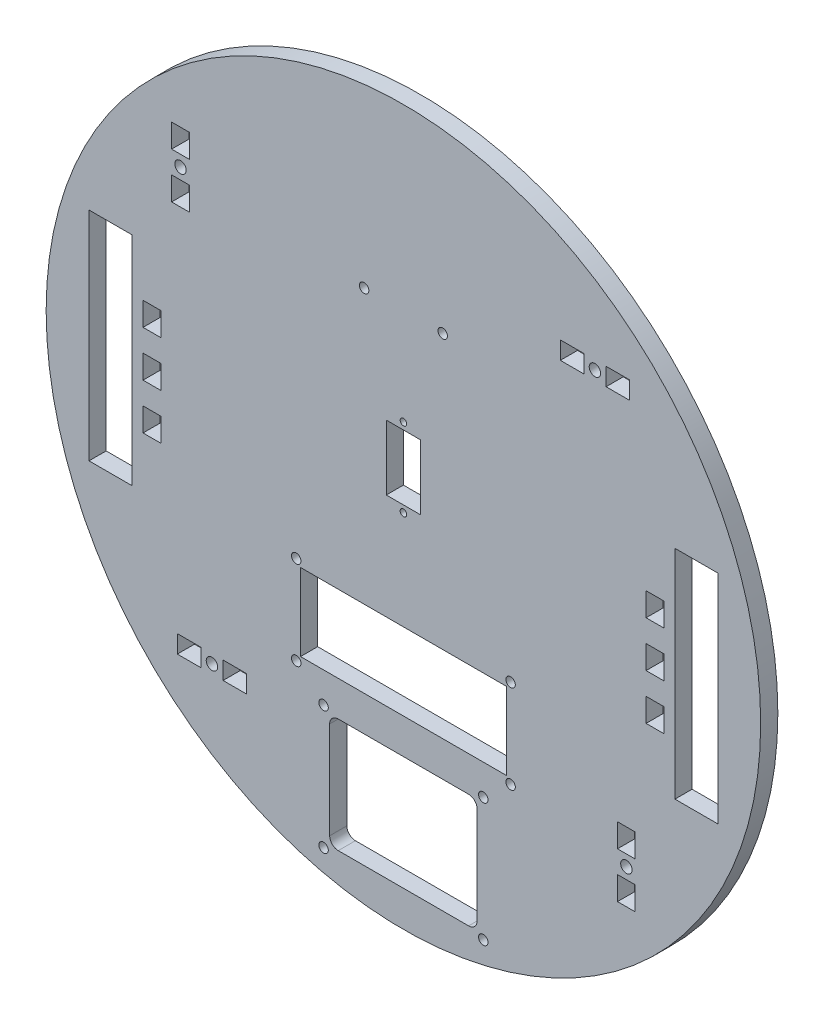
SolidWorks part; units mm, degrees
ref_plane "Plan de face" through (0, 0, 0) normal (0, 0, 1) x (1, 0, 0)
ref_plane "Plan de dessus" through (0, 0, 0) normal (0, 1, 0) x (1, 0, 0)
ref_plane "Plan de droite" through (0, 0, 0) normal (1, 0, 0) x (0, 0, -1)
sketch "Esquisse1" plane through (0, 0, 0) normal (0, 0, 1) x (1, 0, 0)
  line L0 (-125, 0) -> (125, 0) construction
  circle A0 centre (0, 0) radius 125
  dimension "D1" = 250
extrude "Boss.-Extru.1" add sketch "Esquisse1" along normal blind 6
sketch "Esquisse2" plane through (0, 0, 6) normal (0, 0, 1) x (1, 0, 0)
  line L0 (0, 0) -> (-125, 0) construction
  line L1 (-110, 38) -> (-95, 38)
  line L2 (-95, 38) -> (-95, -38)
  line L3 (-110, 38) -> (-110, -38)
  line L4 (-110, -38) -> (-95, -38)
  circle A0 centre (0, 0) radius 125 construction
  dimension "D1" = 38
  dimension "D2" = 38
  dimension "D3" = 15
  dimension "D4" = 95
extrude "Enlèv. mat.-Extru.1" cut sketch "Esquisse2" against normal through all
mirror "Symétrie1" about plane through (0, 0, 0) normal (1, 0, 0) of "Enlèv. mat.-Extru.1"
sketch "Esquisse3" plane through (0, 0, 0) normal (0, 0, -1) x (-1, 0, 0)
  line L0 (-70.9, 78) -> (-63.1, 78) construction
  line L1 (-79.1, 81.1) -> (-70.9, 81.1)
  line L2 (-79.1, 81.1) -> (-79.1, 74.9)
  line L3 (-79.1, 74.9) -> (-70.9, 74.9)
  line L4 (-70.9, 81.1) -> (-70.9, 74.9)
  line L5 (-63.1, 74.9) -> (-54.9, 74.9)
  line L6 (-63.1, 74.9) -> (-63.1, 81.1)
  line L7 (-63.1, 81.1) -> (-54.9, 81.1)
  line L8 (-54.9, 74.9) -> (-54.9, 81.1)
  line L9 (0, 0) -> (0, 69.6176) construction
  line L10 (0, 0) -> (63.3727, 0) construction
  line L11 (-75, 81.1) -> (-75, 74.9) construction
  line L12 (-59, 74.9) -> (-59, 81.1) construction
  circle A0 centre (-67, 78) radius 2
  dimension "D6" = 4
  dimension "D1" = 8.2
  dimension "D2" = 6.2
  dimension "D4" = 8.2
  dimension "D5" = 16
  dimension "D7" = 67
  dimension "D8" = 78
extrude "Enlèv. mat.-Extru.2" cut sketch "Esquisse3" against normal through all
ref_axis "Axe1" through (0, 0, -0.25) along (0, 0, 1)
pattern_circular "Répétition circulaire1" count 4 over 360 about axis through (0, 0, -0.25) along (0, 0, 1) of "Enlèv. mat.-Extru.2"
sketch "Esquisse4" plane through (0, 0, 0) normal (0, 0, -1) x (-1, 0, 0)
  line L0 (-152.6841, 0) -> (161.6648, 0) construction
  line L2 (91.1, 20.1) -> (84.9, 20.1)
  line L3 (91.1, 20.1) -> (91.1, 11.9)
  line L4 (91.1, -20.1) -> (84.9, -20.1)
  line L5 (84.9, 20.1) -> (84.9, 11.9)
  line L6 (84.9, 11.9) -> (91.1, 11.9)
  line L7 (84.9, -4.1) -> (91.1, -4.1)
  line L8 (91.1, 4.1) -> (84.9, 4.1)
  line L9 (84.9, -11.9) -> (91.1, -11.9)
  line L10 (84.9, 4.1) -> (84.9, -4.1)
  line L11 (91.1, 4.1) -> (91.1, -4.1)
  line L12 (84.9, -11.9) -> (84.9, -20.1)
  line L13 (91.1, -11.9) -> (91.1, -20.1)
  line L14 (91.1, -16) -> (84.9, -16) construction
  line L15 (91.1, 16) -> (84.9, 16) construction
  line L16 (88, 20.1) -> (88, -20.1) construction
  line L17 (95, -38) -> (95, 38) construction
  dimension "D1" = 7
  dimension "D2" = 6.2
  dimension "D3" = 32
  dimension "D4" = 16
  dimension "D5" = 8.2
  dimension "D6" = 8.2
  dimension "D8" = 8.2
extrude "Enlèv. mat.-Extru.3" cut sketch "Esquisse4" against normal through all
mirror "Symétrie2" about plane through (0, 0, 0) normal (1, 0, 0) of "Enlèv. mat.-Extru.3"
sketch "Esquisse8" plane through (0, 0, 6) normal (0, 0, 1) x (1, 0, 0)
  line L0 (0, 0) -> (0, -125) construction
  line L1 (-27.94, -72.6176) -> (27.94, -72.6176) construction
  line L2 (-36, -33.306) -> (36, -33.306)
  line L3 (-36, -33.306) -> (-36, -60.306)
  line L4 (-36, -60.306) -> (36, -60.306)
  line L5 (36, -33.306) -> (36, -60.306)
  line L6 (-36, -33.306) -> (36, -60.306) construction
  line L7 (-36, -60.306) -> (36, -33.306) construction
  line L8 (37.5, -62.306) -> (-37.5, -62.306) construction
  line L9 (37.5, -62.306) -> (37.5, -31.306) construction
  line L10 (37.5, -31.306) -> (-37.5, -31.306) construction
  line L11 (-37.5, -62.306) -> (-37.5, -31.306) construction
  line L12 (37.5, -62.306) -> (-37.5, -31.306) construction
  line L13 (37.5, -31.306) -> (-37.5, -62.306) construction
  line L14 (-27.94, -70.9676) -> (27.94, -70.9676) construction
  line L15 (-27.94, -70.9676) -> (-27.94, -114.1476) construction
  line L16 (-27.94, -114.1476) -> (27.94, -114.1476) construction
  line L17 (27.94, -70.9676) -> (27.94, -114.1476) construction
  line L18 (-27.94, -70.9676) -> (27.94, -114.1476) construction
  line L19 (-27.94, -114.1476) -> (27.94, -70.9676) construction
  line L20 (-22.8047, -112.4976) -> (22.8047, -112.4976)
  line L21 (-25.8047, -109.4976) -> (-25.8047, -75.6176)
  line L22 (-22.8047, -72.6176) -> (22.8047, -72.6176)
  line L23 (25.8047, -109.4976) -> (25.8047, -75.6176)
  line L24 (-25.8047, -112.4976) -> (25.8047, -72.6176) construction
  line L25 (-25.8047, -72.6176) -> (25.8047, -112.4976) construction
  circle A0 centre (0, 0) radius 125 construction
  circle A1 centre (-37.5, -31.306) radius 1.65
  circle A2 centre (37.5, -31.306) radius 1.65
  circle A3 centre (37.5, -62.306) radius 1.65
  circle A4 centre (-37.5, -62.306) radius 1.65
  circle A5 centre (-27.94, -70.9676) radius 1.65
  circle A6 centre (27.94, -70.9676) radius 1.65
  circle A7 centre (27.94, -114.1476) radius 1.65
  circle A8 centre (-27.94, -114.1476) radius 1.65
  arc A9 (22.8047, -112.4976) -> (25.8047, -109.4976) centre (22.8047, -109.4976) ccw
  arc A10 (-22.8047, -112.4976) -> (-25.8047, -109.4976) centre (-22.8047, -109.4976) cw
  arc A11 (22.8047, -72.6176) -> (25.8047, -75.6176) centre (22.8047, -75.6176) cw
  arc A12 (-25.8047, -75.6176) -> (-22.8047, -72.6176) centre (-22.8047, -75.6176) cw
  point P6 (0, -46.806)
  point P11 (0, -46.806)
  point P20 (0, -92.5576)
  point P29 (0, -92.5576)
  dimension "D5" = 3.3
  dimension "D6" = 3.3
  dimension "D7" = 3.3
  dimension "D8" = 3.3
  dimension "D11" = 3.3
  dimension "D12" = 3.3
  dimension "D13" = 3.3
  dimension "D14" = 3.3
  dimension "D15" = 3
  dimension "D1" = 27
  dimension "D2" = 72
  dimension "D3" = 75
  dimension "D4" = 31
  dimension "D9" = 55.88
  dimension "D10" = 43.18
extrude "Enlèv. mat.-Extru.4" cut sketch "Esquisse8" against normal up to next
sketch "Esquisse9" plane through (0, 0, 6) normal (0, 0, 1) x (1, 0, 0)
  line L0 (0, 0) -> (0, 125) construction
  line L1 (-13.75, 62.5) -> (13.75, 62.5) construction
  line L2 (-6, 31.05) -> (-6, -1.05) construction
  line L3 (-6, 26.35) -> (6, 26.35)
  line L4 (-6, 26.35) -> (-6, 3.65)
  line L5 (-6, 3.65) -> (6, 3.65)
  line L6 (6, 26.35) -> (6, 3.65)
  line L7 (-6, 26.35) -> (6, 3.65) construction
  line L8 (-6, 3.65) -> (6, 26.35) construction
  line L9 (-6, 31.05) -> (6, 31.05) construction
  line L10 (-6, -1.05) -> (6, -1.05) construction
  line L11 (6, 31.05) -> (6, -1.05) construction
  line L12 (-6, 31.05) -> (6, -1.05) construction
  line L13 (-6, -1.05) -> (6, 31.05) construction
  circle A0 centre (0, 0) radius 125 construction
  circle A1 centre (-13.75, 62.5) radius 1.65
  circle A2 centre (13.75, 62.5) radius 1.65
  circle A3 centre (0, 28.75) radius 1.15
  circle A4 centre (0, 1.25) radius 1.15
  point P8 (0, 62.5)
  point P9 (0, 62.5)
  point P12 (0, 15)
  point P22 (0, 15)
  dimension "D2" = 3.3
  dimension "D3" = 3.3
  dimension "D6" = 2.3
  dimension "D7" = 2.3
  dimension "D1" = 27.5
  dimension "D4" = 22.7
  dimension "D5" = 12
  dimension "D8" = 4.7
  dimension "D9" = 4.7
  dimension "D10" = 2.3
  dimension "D11" = 2.3
  dimension "D12" = 15
extrude "Enlèv. mat.-Extru.5" cut sketch "Esquisse9" against normal up to next
equation "\"D2@Esquisse2\"=\"D1@Esquisse2\""
equation "\"D3@Esquisse6\"=\"D2@Esquisse6\"/2"
equation "\"D18@Esquisse6\"=\"D1@Esquisse6\"/2"
equation "\"D3@Esquisse10\"=\"D2@Esquisse10\"/2"
